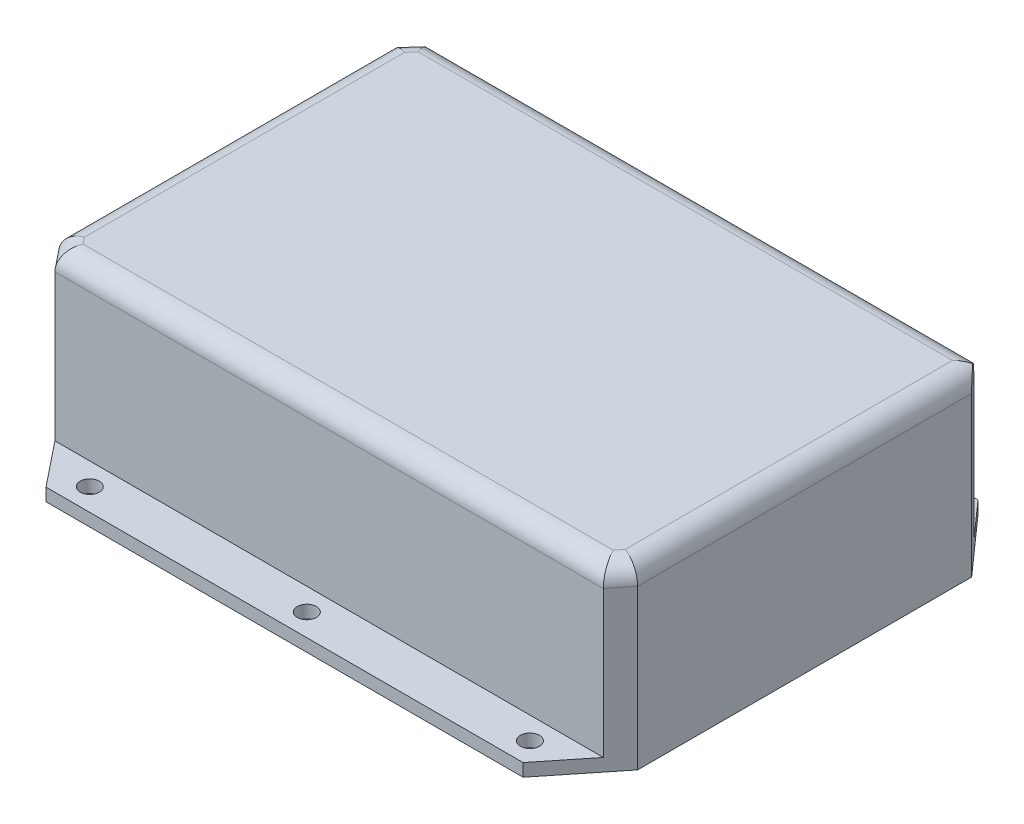
SolidWorks part; units mm, degrees
ref_plane "前视基准面" through (0, 0, 0) normal (0, 0, 1) x (1, 0, 0)
ref_plane "上视基准面" through (0, 0, 0) normal (0, 1, 0) x (1, 0, 0)
ref_plane "右视基准面" through (0, 0, 0) normal (1, 0, 0) x (0, 0, -1)
sketch "草图1" plane through (0, 0, 0) normal (0, 1, 0) x (1, 0, 0)
  line L0 (-91, 58.5) -> (91, 58.5) construction
  line L1 (-85, 52.5) -> (85, 52.5) construction
  line L2 (-85, 52.5) -> (-85, -52.5) construction
  line L3 (-85, -52.5) -> (85, -52.5) construction
  line L4 (85, 52.5) -> (85, -52.5) construction
  line L5 (-85, 52.5) -> (85, -52.5) construction
  line L6 (-85, -52.5) -> (85, 52.5) construction
  line L7 (91, 58.5) -> (91, -58.5) construction
  line L8 (-91, -58.5) -> (91, -58.5) construction
  line L9 (-91, 58.5) -> (-91, -58.5) construction
  line L10 (0, 70.5) -> (0, 58.5) construction
  line L11 (-75, 70.5) -> (75, 70.5)
  line L12 (0, -72.5) -> (0, -58.5) construction
  line L13 (91, 58.5) -> (90.9375, 58.7589)
  line L15 (-75, -72.5) -> (75, -72.5)
  line L17 (-91, 52.5) -> (-75, 70.5)
  line L18 (91, 52.5) -> (75, 70.5)
  line L19 (-91, -52.5) -> (-75, -72.5)
  line L20 (91, -52.5) -> (75, -72.5)
  line L21 (-91, 52.5) -> (-91, -52.5)
  line L22 (91, -52.5) -> (91, 52.5)
  circle A0 centre (0, 64.5) radius 3
  circle A1 centre (-68.2308, 64.5) radius 3
  circle A2 centre (70.1409, 64.5) radius 3
  circle A3 centre (0, -65.5) radius 3
  circle A4 centre (70.1409, -65.5) radius 3
  circle A5 centre (-68.2308, -65.5) radius 3
  point P0 (0, 0)
  point P35 (0, 55.5)
  dimension "D6" = 6
  dimension "D1" = 170
  dimension "D2" = 105
  dimension "D4" = 12
  dimension "D5" = 14
  dimension "D3" = 6
extrude "凸台-拉伸3" add sketch "草图1" along normal blind 4 contours L20 L22 L18 L11 L17 L21 L19 L15 A5 A4 A3 A2 A1 region at (-0.0043, 0, 0.9288)
sketch "草图3" plane through (0, 4, 0) normal (0, 1, 0) x (1, 0, 0)
  line L0 (-91, 52.5) -> (-91, -52.5)
  line L1 (-91, -52.5) -> (-86.2, -58.5)
  line L2 (-91, -52.5) -> (-75, -72.5) construction
  line L3 (-91, -58.5) -> (91, -58.5) construction
  line L4 (-86.2, -58.5) -> (86.2, -58.5)
  line L5 (91, -52.5) -> (75, -72.5) construction
  line L6 (86.2, -58.5) -> (91, -52.5)
  line L7 (91, -52.5) -> (91, 52.5)
  line L8 (91, 52.5) -> (85.6667, 58.5)
  line L9 (91, 52.5) -> (75, 70.5) construction
  line L10 (-91, 58.5) -> (91, 58.5) construction
  line L11 (85.6667, 58.5) -> (-85.6667, 58.5)
  line L12 (-91, 52.5) -> (-75, 70.5) construction
  line L14 (-85.6667, 58.5) -> (-91, 52.5)
  point P0 (0, 0)
  point P7 (0, 0)
extrude "凸台-拉伸5" add sketch "草图3" along normal blind 52
sketch "草图4" plane through (0, 0, 0) normal (0, -1, 0) x (1, 0, 0)
  line L1 (-85, -52.5) -> (85, -52.5)
  line L2 (-85, -52.5) -> (-85, 52.5)
  line L3 (-85, 52.5) -> (85, 52.5)
  line L4 (85, -52.5) -> (85, 52.5)
  line L5 (-85, -52.5) -> (85, 52.5) construction
  line L6 (-85, 52.5) -> (85, -52.5) construction
  point P0 (0, 0)
extrude "切除-拉伸1" cut sketch "草图4" against normal blind 52
fillet "圆角1" radius 6 7 edges at (-88.6, 56, 55.5) (-88.3333, 56, -55.5) (88.6, 56, 55.5) (0, 56, -58.5) (91, 56, 0) (-91, 56, 0) (0, 56, 58.5)
sketch "草图5" plane through (-91, 0, 0) normal (-1, 0, 0) x (0, 0, 1)
  line L0 (0, 0) -> (0, 50) construction
  line L1 (-52.5, 0) -> (52.5, 0) construction
  line L2 (52.5, 50) -> (-52.5, 50) construction
  line L3 (-52.5, 0) -> (52.5, 0) construction
  line L4 (-25, 0) -> (25, 0)
  line L5 (-25, 0) -> (-25, 35)
  line L6 (-20, 40) -> (20, 40)
  line L7 (25, 0) -> (25, 35)
  arc A0 (20, 40) -> (25, 35) centre (20, 35) cw
  arc A1 (-25, 35) -> (-20, 40) centre (-20, 35) cw
  dimension "D4" = 5
  dimension "D1" = 10
  dimension "D2" = 25
  dimension "D3" = 25
extrude "切除-拉伸2" cut sketch "草图5" against normal up to next
